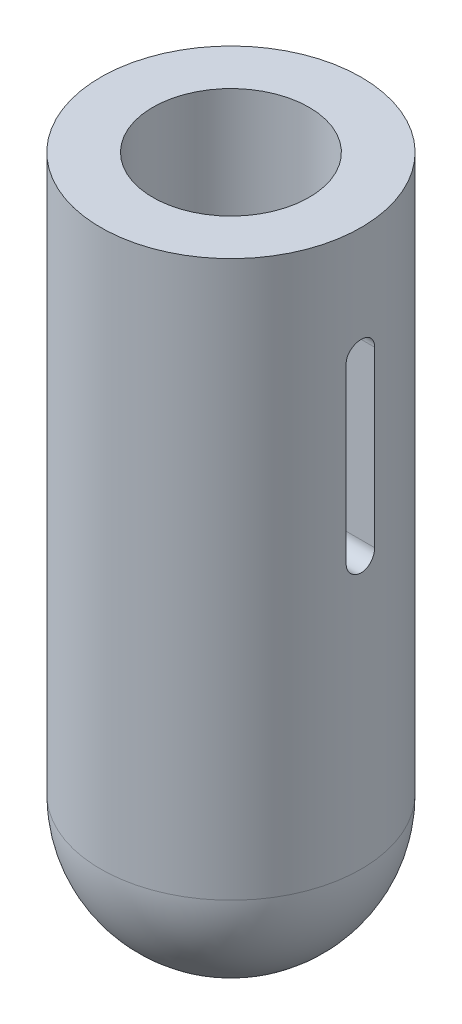
SolidWorks part; units mm, degrees
material "ABS"
ref_plane "Front Plane" through (0, 0, 0) normal (0, 0, 1) x (1, 0, 0)
ref_plane "Top Plane" through (0, 0, 0) normal (0, 1, 0) x (1, 0, 0)
ref_plane "Right Plane" through (0, 0, 0) normal (1, 0, 0) x (0, 0, -1)
sketch "Sketch1" plane through (0, 0, 0) normal (1, 0, 0) x (0, 0, -1)
  line L0 (0, -1981.5228) -> (0, 97024.9941) construction
  line L1 (11.25, 0) -> (18.75, 0)
  line L2 (18.75, 0) -> (18.75, -80)
  line L3 (11.25, 0) -> (11.25, -80)
  line L4 (11.25, -80) -> (0, -80)
  line L5 (0, -80) -> (0, -98.75)
  line L6 (0, -16) -> (0, -41) construction
  line L7 (2.05, -16) -> (2.05, -41)
  line L8 (-2.05, -16) -> (-2.05, -41)
  arc A0 (18.75, -80) -> (0, -98.75) centre (0, -80) cw
  arc A1 (2.05, -16) -> (-2.05, -16) centre (0, -16) ccw
  arc A2 (-2.05, -41) -> (2.05, -41) centre (0, -41) ccw
  point P12 (0, -28.5)
  dimension "D1" = 22.5
  dimension "D2" = 7.5
  dimension "D3" = 80
  dimension "D4" = 4.1
  dimension "D5" = 25
  dimension "D6" = 16
revolve "Revolve1" add sketch "Sketch1" angle 360 about L0 region at (0, -55.1143, -12.7806)
extrude "Cut-Extrude1" cut sketch "Sketch1<3>" against normal through all both and the other way through all contours L8 A2 L7 A1 region at (0, -28.5, 0)
sketch "Sketch1<3>" plane through (0, 0, 0) normal (1, 0, 0) x (0, 0, -1) same geometry as "Sketch1"
